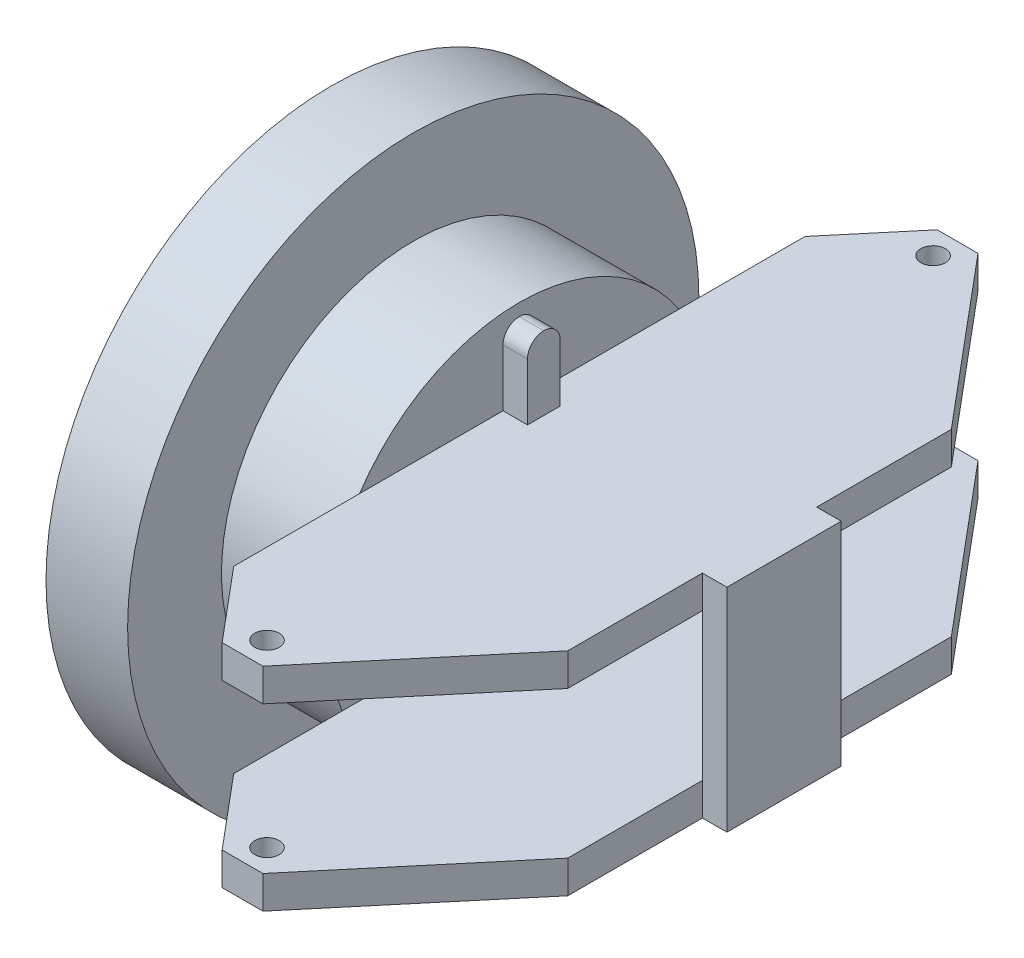
SolidWorks part; units mm, degrees
material "6061-T6 (SS)"
ref_plane "Front Plane" through (0, 0, 0) normal (0, 0, 1) x (1, 0, 0)
ref_plane "Top Plane" through (0, 0, 0) normal (0, 1, 0) x (1, 0, 0)
ref_plane "Right Plane" through (0, 0, 0) normal (1, 0, 0) x (0, 0, -1)
sketch "Sketch1" plane through (0, 0, 0) normal (1, 0, 0) x (0, 0, -1)
  circle A0 centre (0, 0) radius 35
  dimension "D1" = 70
extrude "Boss-Extrude1" add sketch "Sketch1" along normal blind 10
sketch "Sketch2" plane through (10, 0, 0) normal (1, 0, 0) x (0, 0, -1)
  circle A0 centre (0, 0) radius 23.5
  dimension "D1" = 47
extrude "Boss-Extrude2" add sketch "Sketch2" along normal blind 13
ref_plane "Plane1" through (0, 13, 0) normal (0, 1, 0) x (1, 0, 0)
sketch "Sketch3" plane through (0, 13, 0) normal (0, 1, 0) x (1, 0, 0)
  line L0 (23, 35) -> (23, -35)
  line L1 (23, -23.5) -> (23, 23.5) construction
  line L2 (23, -35) -> (30.3921, -43.8095)
  line L3 (30.3921, -43.8095) -> (35.3921, -43.8095)
  line L4 (35.3921, -43.8095) -> (52.4338, -23.5)
  line L5 (52.4338, -23.5) -> (52.4338, 23.5)
  line L6 (52.4338, 0) -> (23, 0) construction
  line L7 (35.3921, 43.8095) -> (52.4338, 23.5)
  line L8 (30.3921, 43.8095) -> (35.3921, 43.8095)
  line L9 (23, 35) -> (30.3921, 43.8095)
  line L10 (23, -23.5) -> (55.5553, -23.5) construction
  line L11 (10, -23.5) -> (23, -23.5) construction
  dimension "D1" = 35
  dimension "D2" = 11.5
  dimension "D3" = 40
  dimension "D4" = 5
  dimension "D5" = 50
extrude "Boss-Extrude3" add sketch "Sketch3" against normal blind 4
sketch "Sketch5" plane through (0, 9, 0) normal (0, -1, 0) x (-1, 0, 0)
  line L0 (-30.3921, -43.8095) -> (-35.3921, -43.8095) construction
  line L1 (-32.8921, -43.8095) -> (-32.8921, -40.8095) construction
  circle A0 centre (-32.8921, -40.8095) radius 1.5
  dimension "D1" = 3
  dimension "D2" = 3
extrude "Cut-Extrude1" cut sketch "Sketch5" against normal blind 4
mirror "Mirror1" about plane through (0, 0, 0) normal (0, 0, 1) of "Cut-Extrude1"
mirror "Mirror3" about plane through (0, 0, 0) normal (0, 1, 0) of "Mirror1", "Cut-Extrude1", "Boss-Extrude3"
sketch "Sketch8" plane through (23, 0, 0) normal (1, 0, 0) x (0, 0, -1)
  line L0 (0, 13) -> (0, 23.5) construction
  line L1 (19.5768, 13) -> (-19.5768, 13) construction
  line L2 (-2, 13) -> (-2, 22)
  line L3 (-2, 22) -> (2, 22)
  line L4 (2, 22) -> (2, 13)
  line L5 (2, 13) -> (-2, 13)
  arc A0 (19.5768, 13) -> (-19.5768, 13) centre (0, 0) ccw construction
  dimension "D1" = 9
  dimension "D2" = 2
  dimension "D3" = 2
extrude "Boss-Extrude4" add sketch "Sketch8" along normal blind 3
fillet "Fillet1" radius 2 2 edges at (24.5, 22, 2) (24.5, 22, -2)
mirror "Mirror4" about plane through (0, 0, 0) normal (0, 1, 0) of "Fillet1", "Boss-Extrude4"
sketch "Sketch9" plane through (52.4338, 0, 0) normal (1, 0, 0) x (0, 0, -1)
  line L1 (-7, -13) -> (7, -13)
  line L2 (-7, -13) -> (-7, 13)
  line L3 (-7, 13) -> (7, 13)
  line L4 (7, -13) -> (7, 13)
  line L5 (-7, -13) -> (7, 13) construction
  line L6 (-7, 13) -> (7, -13) construction
  point P0 (0, 0)
  dimension "D1" = 14
  dimension "D2" = 26
extrude "Boss-Extrude5" add sketch "Sketch9" along normal blind 3
sketch "Sketch10" plane through (0, 0, 0) normal (-1, 0, 0) x (0, 0, 1)
  circle A0 centre (0, 0) radius 10
  dimension "D1" = 20
extrude "Cut-Extrude2" cut sketch "Sketch10" against normal blind 10
